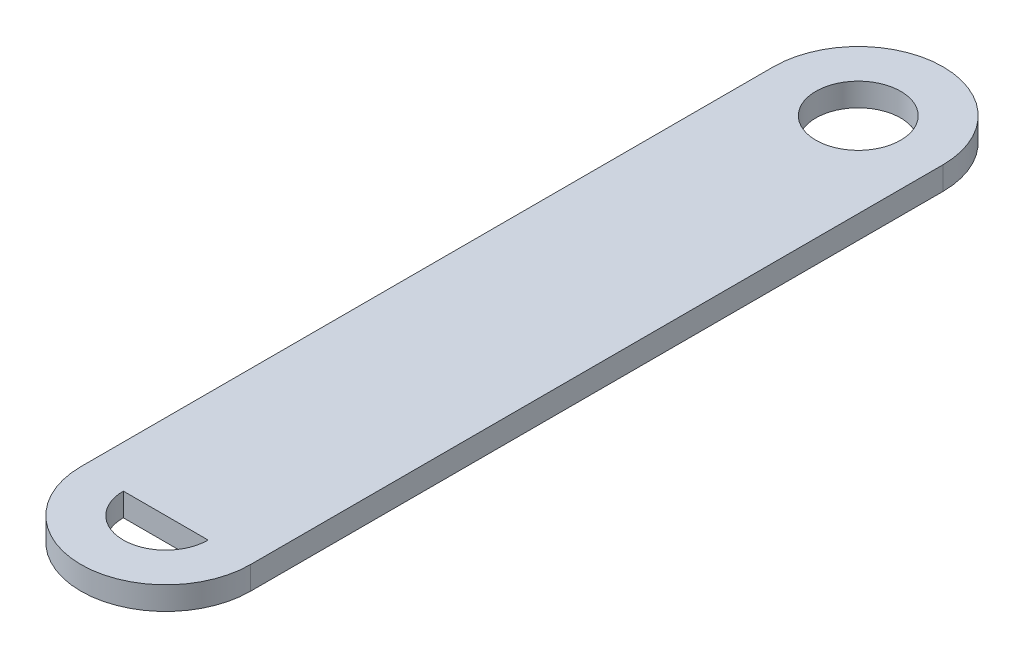
SolidWorks part; units mm, degrees
ref_plane "Front Plane" through (0, 0, 0) normal (0, 0, 1) x (1, 0, 0)
ref_plane "Top Plane" through (0, 0, 0) normal (0, 1, 0) x (1, 0, 0)
ref_plane "Right Plane" through (0, 0, 0) normal (1, 0, 0) x (0, 0, -1)
sketch "Sketch2" plane through (0, 0, 0) normal (0, 1, 0) x (1, 0, 0)
  line L0 (0, 159.1686) -> (0, -18.2675) construction
  line L1 (-11, 89.0713) -> (-11, -0.7487)
  line L2 (11, 89.0713) -> (11, -0.7487)
  line L4 (-5.5, -0.7487) -> (5.5, -0.7487)
  arc A0 (-11, 89.0713) -> (11, 89.0713) centre (0, 89.0713) cw
  arc A1 (-11, -0.7487) -> (11, -0.7487) centre (0, -0.7487) ccw
  circle A2 centre (0, 89.0713) radius 5.5
  arc A4 (5.5, -0.7487) -> (-5.5, -0.7487) centre (0, -0.7487) cw
  point P9 (0, 0)
  point P10 (0, 0)
  point P15 (0, 0)
  point P16 (0, 1.6013)
  point P17 (0, -1.5543)
  point P18 (0, 0)
  point P19 (0, 159.1686)
  point P20 (0, -16.6702)
  point P21 (0, -18.2675)
  point P22 (0, 0)
  point P23 (0, 0)
  dimension "D1" = 11
  dimension "D2" = 11
  dimension "D4" = 89.82
  dimension "D3" = 11
extrude "Boss-Extrude1" add sketch "Sketch2" along normal blind 3
